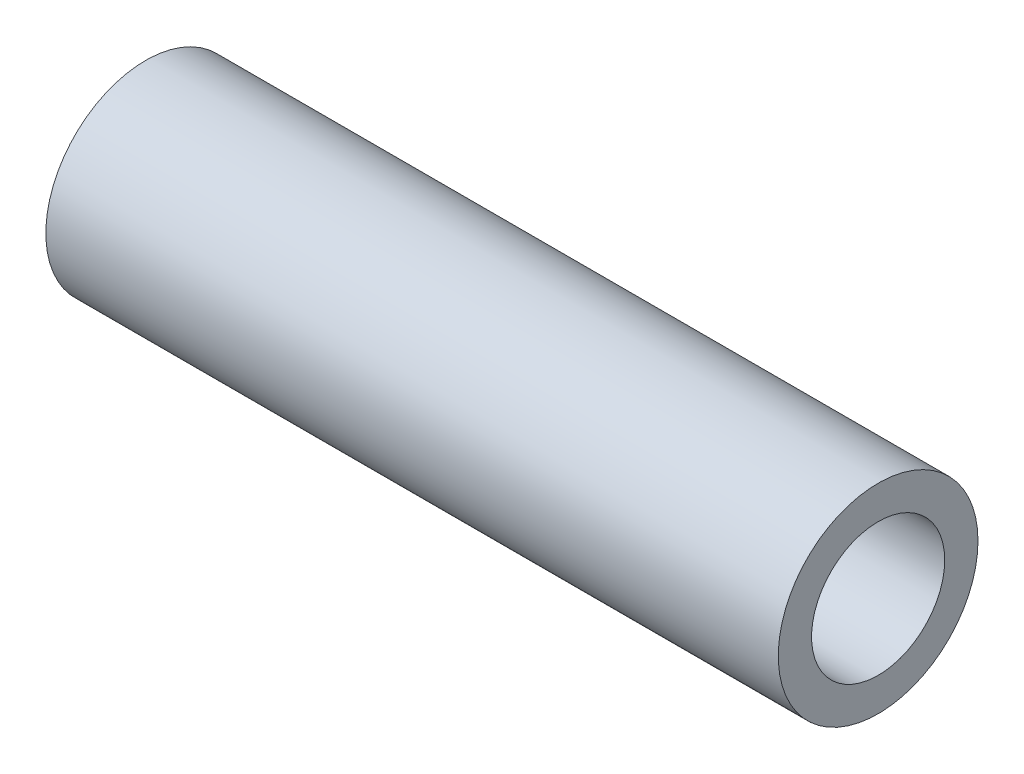
SolidWorks part; units mm, degrees
material "AISI 1035 Steel (SS)"
ref_plane "Front Plane" through (0, 0, 0) normal (0, 0, 1) x (1, 0, 0)
ref_plane "Top Plane" through (0, 0, 0) normal (0, 1, 0) x (1, 0, 0)
ref_plane "Right Plane" through (0, 0, 0) normal (1, 0, 0) x (0, 0, -1)
sketch "Sketch1" plane through (0, 0, 0) normal (1, 0, 0) x (0, 0, -1)
  circle A0 centre (0, 0) radius 7.0561
  circle A1 centre (0, 0) radius 4.7041
extrude "Boss-Extrude1" add sketch "Sketch1" along normal blind 25.8762 and the other way blind 25.8762
